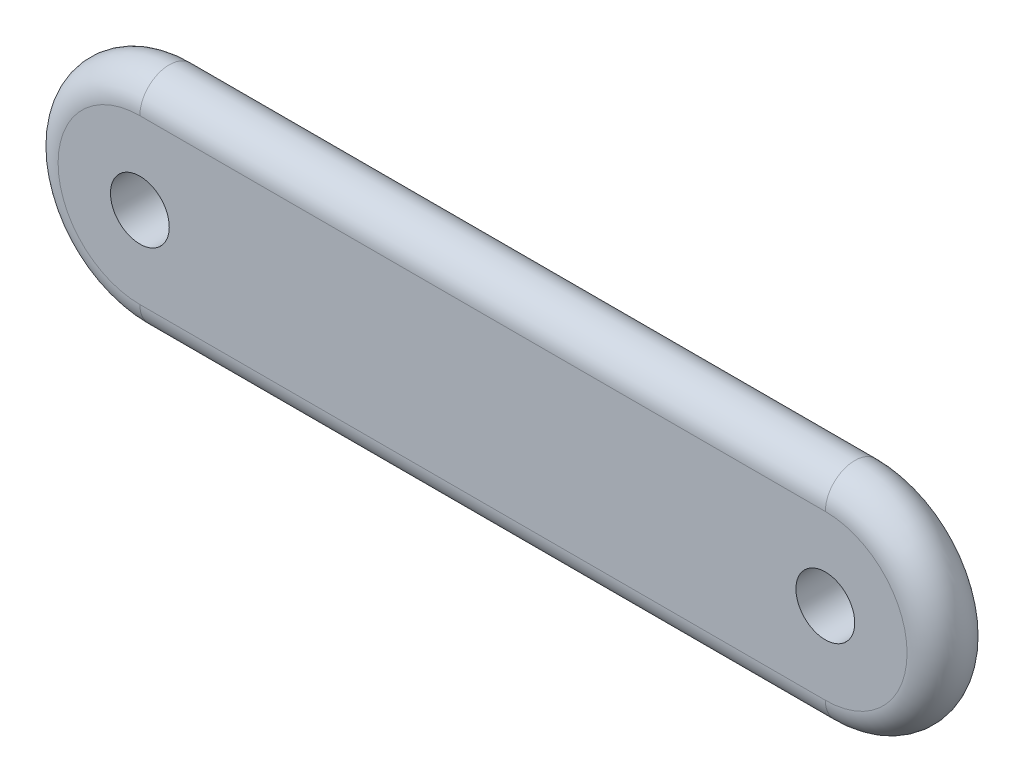
SolidWorks part; units mm, degrees
ref_plane "XY" through (0, 0, 0) normal (0, 0, 1) x (1, 0, 0)
ref_plane "XZ" through (0, 0, 0) normal (0, 1, 0) x (1, 0, 0)
ref_plane "YZ" through (0, 0, 0) normal (1, 0, 0) x (0, 0, -1)
ref_axis "X" through (-88.99, 0, 0) along (1, 0, 0)
ref_axis "Y" through (0, -55, 0) along (0, 1, 0)
ref_axis "Z" through (0, 0, 55) along (0, 0, -1)
sketch "Sketch1" plane through (0, 0, 0) normal (0, 0, 1) x (1, 0, 0)
  line L0 (-37, 0) -> (37, 0) construction
  line L1 (-37, 12) -> (37, 12)
  line L2 (-37, -12) -> (37, -12)
  arc A0 (-37, 12) -> (-37, -12) centre (-37, 0) ccw
  arc A1 (37, -12) -> (37, 12) centre (37, 0) ccw
  point P2 (0, 0)
  dimension "D2" = 12
  dimension "D1" = 74
extrude "Boss-Extrude1" add sketch "Sketch1" along normal blind 6.35
hole_wizard "1/4 (0.25) Diameter Hole1" positions "Sketch2" profile "Sketch3" hole size "1/4" standard "ANSI Inch" end condition through all
sketch "Sketch2" plane through (0, 0, 6.35) normal (0, 0, 1) x (1, 0, 0)
  point P0 (-37, 0)
  point P2 (37, 0)
  point P5 (-37, 0)
  point P7 (37, 0)
sketch "Sketch3" plane through (-37, 0, 6.35) normal (1, 0, 0) x (0, -1, 0)
  line L0 (0, 0) -> (0, 6.35)
  line L1 (0, 6.35) -> (3.175, 6.35)
  line L2 (3.175, 6.35) -> (3.175, 0)
  line L5 (3.175, 0) -> (0, 0)
  line L11 (0, -6.35) -> (0, 107.95) construction
  dimension "Thru Hole Dia." = 6.35
  dimension "Thru Hole Depth" = 6.35
fillet "Fillet1" 2 edges at (0, -12, 6.35) (0, -12, 0) type full round first side face at (-33.825, 0, 6.35) second side face at (-33.825, 0, 0) middle face at (0, -12, 3.175)
